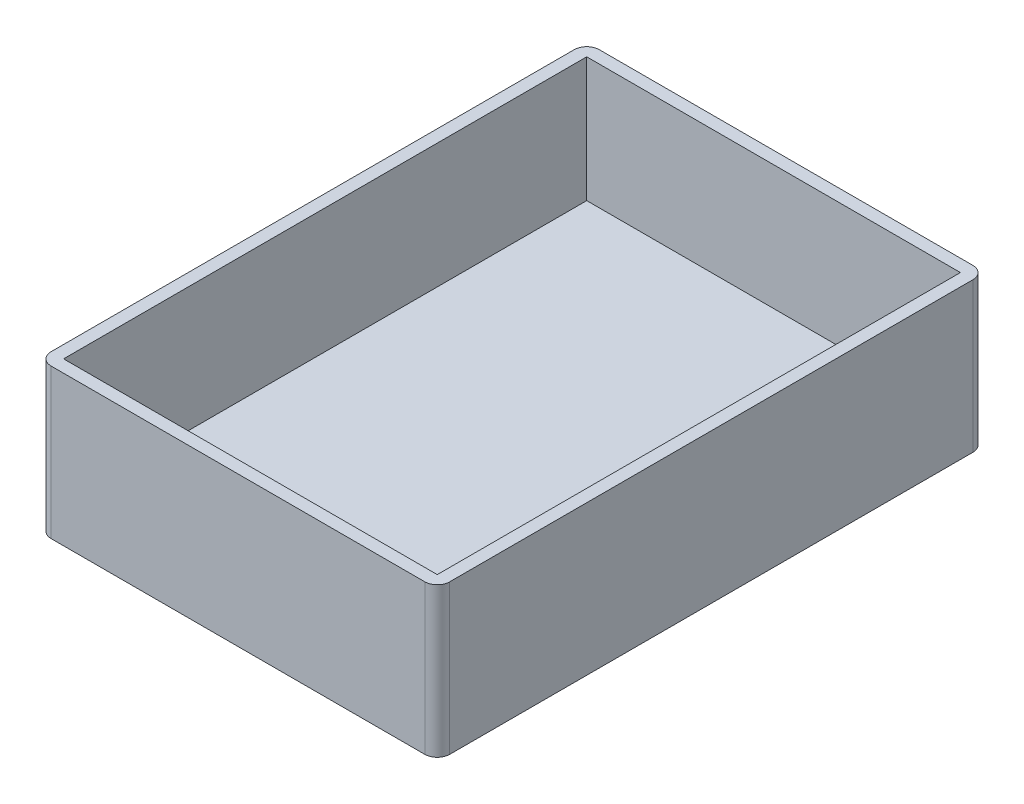
SolidWorks part; units mm, degrees
ref_plane "Front Plane" through (0, 0, 0) normal (0, 0, 1) x (1, 0, 0)
ref_plane "Top Plane" through (0, 0, 0) normal (0, 1, 0) x (1, 0, 0)
ref_plane "Right Plane" through (0, 0, 0) normal (1, 0, 0) x (0, 0, -1)
sketch "Main Body" plane through (0, 0, 0) normal (0, 1, 0) x (1, 0, 0)
  line L0 (-75, 110) -> (75, 110)
  line L1 (-75, -105) -> (75, -105)
  line L2 (-75, -105) -> (-75, 105)
  line L3 (-75, 105) -> (75, 105)
  line L4 (75, -105) -> (75, 105)
  line L5 (-75, -105) -> (75, 105) construction
  line L6 (-75, 105) -> (75, -105) construction
  line L7 (80, -105) -> (80, 105)
  line L8 (-75, -110) -> (75, -110)
  line L9 (-80, -105) -> (-80, 105)
  line L10 (-80, -110) -> (80, -110) construction
  line L11 (-80, -110) -> (-80, 110) construction
  line L12 (80, -110) -> (80, 110) construction
  line L13 (-80, 110) -> (80, 110) construction
  arc A0 (-75, -110) -> (-80, -105) centre (-75, -105) cw
  arc A1 (80, -105) -> (75, -110) centre (75, -105) cw
  arc A2 (75, 110) -> (80, 105) centre (75, 105) cw
  arc A3 (-75, 110) -> (-80, 105) centre (-75, 105) ccw
  point P0 (0, 0)
  dimension "D4" = 5
  dimension "D1" = 75
  dimension "D2" = 210
  dimension "D3" = 5
extrude "Boss-Extrude1" add sketch "Main Body" along normal blind 10 contours L1 L4 L3 L2 | L9 L8 L7 L0 L4 L1 L2 L3 region at (0, 0, -107.2797) region at (0, 0, 0)
extrude "Boss-Extrude3" add sketch "Main Body<4>" along normal blind 50 from surface starting at face at (0, 10, 0)
sketch "Main Body<4>" plane through (0, 0, 0) normal (0, 1, 0) x (1, 0, 0) same geometry as "Main Body"
sketch "Sketch1" plane through (75, 0, 0) normal (-1, 0, 0) x (0, 0, 1)
  line L0 (105, 60) -> (105, 10) construction
  line L1 (-105, 10) -> (105, 10) construction
  line L2 (80, 17.5) -> (105, 17.5)
  line L3 (80, 10) -> (105, 10)
  line L4 (80, 10) -> (80, 35)
  line L5 (80, 35) -> (105, 35)
  line L6 (105, 10) -> (105, 35)
  line L7 (80, 10) -> (105, 35) construction
  line L8 (80, 35) -> (105, 10) construction
  circle A0 centre (92.5, 22.5) radius 12.5
  line M2 (-105, 10) -> (105, 10)
  line M3 (105, 10) -> (105, 60)
  dimension "D1" = 25
  dimension "D2" = 7.5
extrude "Boss-Extrude4" add sketch "Sketch1" along normal up to surface (150 mm away) contours A0 L4 M2 | A0 L3 M3 region at (75, 12.4727, 82.9254) region at (75, 12.4727, 102.0746) up to face at (-75, 35, 0)
sketch "Sketch2" plane through (0, 0, 0) normal (1, 0, 0) x (0, 0, -1)
  line L0 (-105, 60) -> (-105, 17.5) construction
  line L1 (-105, 10) -> (-80, 10)
  line L2 (-105, 10) -> (-105, 17.5)
  line L3 (-105, 17.5) -> (-80, 17.5)
  line L4 (-80, 10) -> (-80, 17.5)
  line L5 (105, 10) -> (-80, 10) construction
  line L6 (-80, 10) -> (-80, 17.5) construction
  line L7 (-80, 17.5) -> (-81.0436, 17.5) construction
  point P4 (0, 0)
  point P7 (-65.3113, 29.4968)
extrude "Cut-Extrude1" cut sketch "Sketch2" against normal mid plane 10
sketch "Sketch3" plane through (0, 10, 0) normal (0, 1, 0) x (1, 0, 0)
  line L0 (75, -105) -> (-75, -105) construction
  line L1 (-5, -80) -> (-10, -80)
  line L2 (-5, -80) -> (-5, -105)
  line L3 (-5, -105) -> (-10, -105)
  line L4 (-10, -80) -> (-10, -105)
  line L5 (0, 0) -> (0, -105) construction
  line L6 (-75, -80) -> (-5, -80) construction
  line L7 (10, -80) -> (10, -105)
  line L8 (5, -105) -> (10, -105)
  line L9 (5, -80) -> (5, -105)
  line L10 (5, -80) -> (10, -80)
  point P10 (-8.4994, -80)
  dimension "D1" = 5
extrude "Boss-Extrude5" add sketch "Sketch3" along normal up to surface (7.5 mm away) up to face at (40, 17.5, 80.5218)
